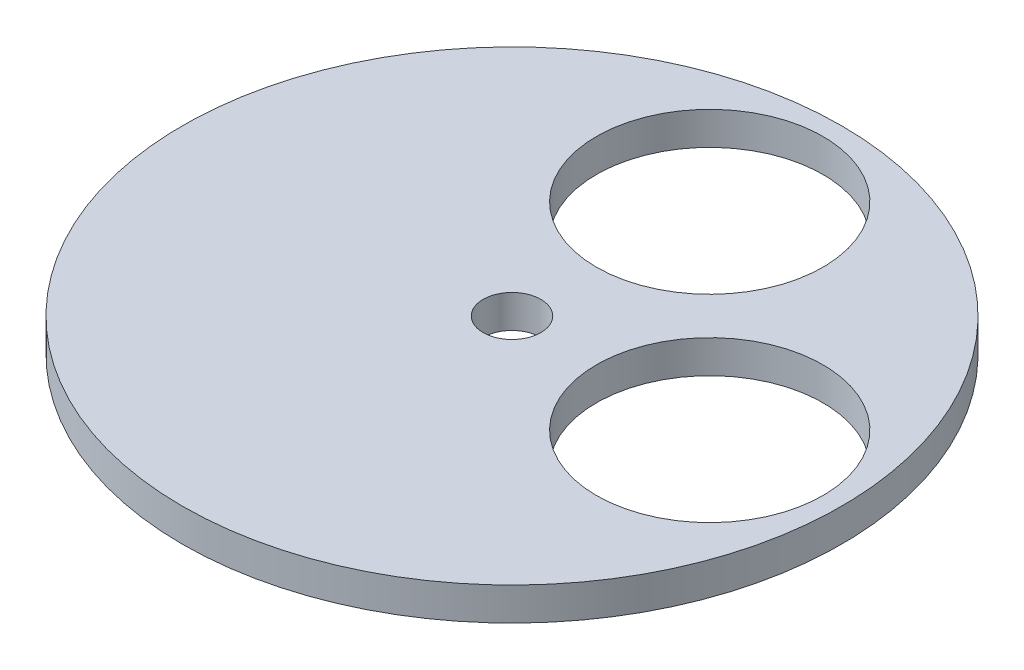
SolidWorks part; units mm, degrees
ref_plane "Front Plane" through (0, 0, 0) normal (0, 0, 1) x (1, 0, 0)
ref_plane "Top Plane" through (0, 0, 0) normal (0, 1, 0) x (1, 0, 0)
ref_plane "Right Plane" through (0, 0, 0) normal (1, 0, 0) x (0, 0, -1)
sketch "Sketch6" plane through (0, 0, 0) normal (0, 1, 0) x (1, 0, 0)
  circle A2 centre (63.5, 63.5) radius 50.8
  dimension "D1" = 101.6
extrude "Boss-Extrude3" add sketch "Sketch6" along normal blind 5.08 contours A2
sketch "Sketch11" plane through (0, 5.08, 0) normal (0, 1, 0) x (1, 0, 0)
  line L0 (63.5, 114.3) -> (63.5, 63.5)
  line L1 (63.5, 63.5) -> (114.3, 63.5)
  circle A0 centre (63.5, 93.98) radius 17.4625
  circle A1 centre (93.98, 63.5) radius 17.4625
  circle A2 centre (63.5, 63.5) radius 50.8 construction
  dimension "D1" = 34.925
  dimension "D2" = 20.32
  dimension "D3" = 20.32
extrude "Cut-Extrude2" cut sketch "Sketch11" against normal through all contours L0 A0 | L0 A0 | L1 A1 | L1 A1 | A0 region at (70.9113, 5.08, -93.98) region at (93.98, 5.08, -70.9113) region at (93.98, 5.08, -56.0887) region at (56.0887, 5.08, -93.98)
sketch "Sketch12" plane through (0, 5.08, 0) normal (0, 1, 0) x (1, 0, 0)
  circle A0 centre (63.5, 63.5) radius 4.445
  dimension "D1" = 8.89
extrude "Cut-Extrude3" cut sketch "Sketch12" against normal through all contours A0
